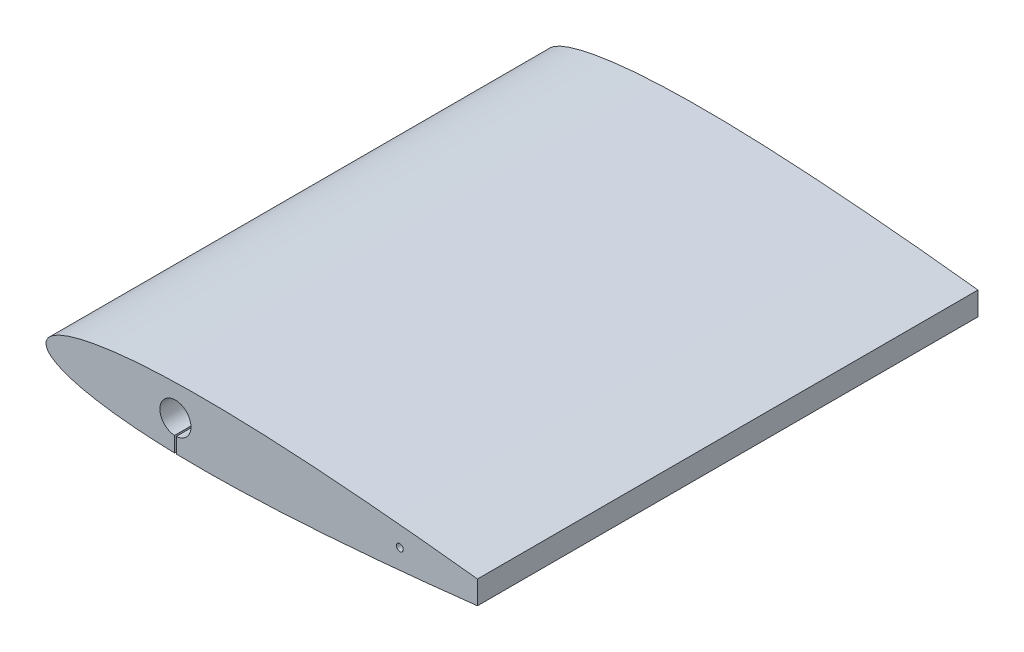
SolidWorks part; units mm, degrees
material "UoS Blue Foam"
ref_plane "Front Plane" through (0, 0, 0) normal (0, 0, 1) x (1, 0, 0)
ref_plane "Top Plane" through (0, 0, 0) normal (0, 1, 0) x (1, 0, 0)
ref_plane "Right Plane" through (0, 0, 0) normal (1, 0, 0) x (0, 0, -1)
sketch "Sketch5" plane through (0, 0, 0) normal (0, 0, 1) x (1, 0, 0)
  line L1 (300, 0.378) -> (300, -0.378)
  spline S1 degree 3 poles (300, 0.378) (299.2704, 0.4794) (297.2347, 0.7625) (293.6597, 1.2577) (289.1124, 1.8742) (284.0808, 2.5445) (278.752, 3.2381) (273.2659, 3.9349) (267.706, 4.629) (262.1146, 5.3131) (256.5083, 5.9822) (250.8917, 6.638) (245.2696, 7.2818) (239.6473, 7.9122) (234.0251, 8.527) (228.3991, 9.1262) (222.7683, 9.7131) (217.1359, 10.2875) (211.5054, 10.8469) (205.8776, 11.3916) (200.2515, 11.9209) (194.6264, 12.4346) (189.0028, 12.9319) (183.3815, 13.4131) (177.7632, 13.8764) (172.1483, 14.3212) (166.5375, 14.7478) (160.9317, 15.1542) (155.3317, 15.5391) (149.7375, 15.9026) (144.1487, 16.2418) (138.5657, 16.5574) (132.9909, 16.8474) (127.4274, 17.1102) (121.8776, 17.3439) (116.3408, 17.5453) (110.8155, 17.7127) (105.3013, 17.8445) (99.8006, 17.9401) (94.3174, 17.9966) (88.8558, 18.0101) (83.4186, 17.9792) (78.0085, 17.8992) (72.6285, 17.767) (67.2827, 17.5794) (61.9774, 17.3315) (56.7207, 17.021) (51.5252, 16.641) (46.4082, 16.1902) (41.3942, 15.6617) (36.5157, 15.054) (31.819, 14.3656) (27.3662, 13.6035) (23.2352, 12.7826) (19.5026, 11.9203) (16.2183, 11.0446) (13.3892, 10.1751) (10.9849, 9.3335) (8.9616, 8.5221) (7.2673, 7.747) (5.8461, 7.0106) (4.6477, 6.3006) (3.6282, 5.6065) (2.7519, 4.9266) (2.0063, 4.2499) (1.3906, 3.5703) (0.901, 2.8909) (0.5293, 2.2202) (0.2605, 1.5665) (0.0857, 0.931) (-0.0035, 0.309) (-0.0035, -0.309) (0.0857, -0.931) (0.2605, -1.5665) (0.5293, -2.2202) (0.901, -2.8909) (1.3906, -3.5703) (2.0063, -4.2499) (2.7519, -4.9266) (3.6282, -5.6065) (4.6477, -6.3006) (5.8461, -7.0106) (7.2673, -7.747) (8.9616, -8.5221) (10.9849, -9.3335) (13.3892, -10.1751) (16.2183, -11.0446) (19.5026, -11.9203) (23.2352, -12.7826) (27.3661, -13.6036) (31.8191, -14.3651) (36.5156, -15.0541) (41.3942, -15.6616) (46.4082, -16.1902) (51.5252, -16.641) (56.7207, -17.021) (61.9774, -17.3315) (67.2827, -17.5794) (72.6285, -17.767) (78.0085, -17.8992) (83.4186, -17.9792) (88.8558, -18.0101) (94.3174, -17.9966) (99.8006, -17.9401) (105.3013, -17.8445) (110.8155, -17.7127) (116.3408, -17.5453) (121.8776, -17.3439) (127.4274, -17.1102) (132.9909, -16.8474) (138.5657, -16.5574) (144.1487, -16.2418) (149.7375, -15.9026) (155.3317, -15.5391) (160.9317, -15.1542) (166.5375, -14.7478) (172.1483, -14.3212) (177.7632, -13.8764) (183.3815, -13.4131) (189.0028, -12.9319) (194.6264, -12.4346) (200.2515, -11.9209) (205.8776, -11.3916) (211.5054, -10.8469) (217.1359, -10.2875) (222.7683, -9.7131) (228.3991, -9.1262) (234.0251, -8.527) (239.6473, -7.9122) (245.2696, -7.2818) (250.8917, -6.638) (256.5083, -5.9822) (262.1146, -5.3131) (267.706, -4.629) (273.2659, -3.9349) (278.752, -3.2381) (284.0808, -2.5445) (289.1124, -1.8742) (293.6597, -1.2577) (297.2347, -0.7625) (299.2704, -0.4794) (300, -0.378) knots 0 0 0 0 0.003612 0.010079 0.017699 0.026115 0.034971 0.04405 0.053234 0.062448 0.071674 0.080921 0.090178 0.099424 0.108664 0.117912 0.12717 0.136427 0.145675 0.154916 0.164153 0.173387 0.182616 0.191838 0.201053 0.21026 0.219459 0.228647 0.237822 0.246985 0.256137 0.265279 0.274407 0.283512 0.292592 0.301646 0.310682 0.319699 0.328695 0.33766 0.346589 0.355477 0.364323 0.373122 0.381868 0.390553 0.399166 0.40769 0.416098 0.424355 0.432412 0.440205 0.447631 0.454564 0.460855 0.466413 0.471229 0.475366 0.478901 0.481915 0.484499 0.486747 0.488741 0.490543 0.492182 0.493673 0.495032 0.496279 0.497425 0.49849 0.499503 0.500497 0.50151 0.502575 0.503721 0.504968 0.506327 0.507818 0.509457 0.511259 0.513253 0.515501 0.518085 0.521099 0.524634 0.528771 0.533587 0.539145 0.545436 0.55237 0.559795 0.567588 0.575645 0.583902 0.59231 0.600834 0.609447 0.618132 0.626878 0.635677 0.644523 0.653411 0.66234 0.671305 0.680301 0.689318 0.698354 0.707408 0.716488 0.725593 0.734721 0.743863 0.753015 0.762178 0.771353 0.780541 0.78974 0.798947 0.808162 0.817384 0.826613 0.835847 0.845084 0.854325 0.863573 0.87283 0.882088 0.891336 0.900576 0.909822 0.919079 0.928326 0.937552 0.946766 0.95595 0.965029 0.973885 0.982301 0.989921 0.996388 1 1 1 1
  dimension "Tail chord" = 300
extrude "Boss-Extrude1" add sketch "Sketch5" along normal blind 290
ref_plane "Plane1" through (0, 0, 290) normal (0, 0, 1) x (1, 0, 0)
sketch "Sketch7" plane through (0, 0, 290) normal (0, 0, 1) x (1, 0, 0)
  line L0 (-6.7213, 0) -> (341.1075, 0) construction
  line L1 (300, -35.2391) -> (300, 43.1318) construction
  line L2 (300, -0.378) -> (300, 0.378) construction
  line L3 (0, 36.9496) -> (0, -37.0407) construction
  circle A0 centre (75, 0) radius 9
  dimension "D1" = 18
  dimension "Tail chord quarter" = 75
extrude "Cut-Extrude7" cut sketch "Sketch7" against normal through all
curve "Curve6"
  spline degree 3 poles (298.242, -0.1932, 0) (300.4407, 0, 0) (298.242, 0.1932, 0) (296.4349, 0.5367, 0) (292.0253, 1.0976, 0) (286.5771, 1.8592, 0) (279.4156, 2.8001, 0) (270.9173, 3.8949, 0) (261.066, 5.1159, 0) (250.0071, 6.4339, 0) (237.8495, 7.8187, 0) (224.7304, 9.2395, 0) (210.7923, 10.6647, 0) (196.1883, 12.0613, 0) (181.0783, 13.3946, 0) (165.6277, 14.6278, 0) (150.0058, 15.7225, 0) (134.3834, 16.6392, 0) (118.9317, 17.3387, 0) (103.8195, 17.7845, 0) (89.2123, 17.9443, 0) (75.2698, 17.7935, 0) (62.1444, 17.3161, 0) (49.9793, 16.5075, 0) (38.907, 15.374, 0) (29.0471, 13.9333, 0) (20.5034, 12.2128, 0) (13.3641, 10.246, 0) (7.6828, 8.0707, 0) (3.4992, 5.7028, 0) (0.7348, 3.1014, 0) (-0.3264, 0, 0) (0.7348, -3.1014, 0) (3.4992, -5.7028, 0) (7.6828, -8.0707, 0) (13.3641, -10.246, 0) (20.5034, -12.2128, 0) (29.0471, -13.9333, 0) (38.907, -15.374, 0) (49.9793, -16.5075, 0) (62.1444, -17.3161, 0) (75.2698, -17.7935, 0) (89.2123, -17.9443, 0) (103.8195, -17.7845, 0) (118.9317, -17.3387, 0) (134.3834, -16.6392, 0) (150.0058, -15.7225, 0) (165.6277, -14.6278, 0) (181.0783, -13.3946, 0) (196.1883, -12.0613, 0) (210.7923, -10.6647, 0) (224.7304, -9.2395, 0) (237.8495, -7.8187, 0) (250.0071, -6.4339, 0) (261.066, -5.1159, 0) (270.9173, -3.8949, 0) (279.4156, -2.8001, 0) (286.5771, -1.8592, 0) (292.0253, -1.0976, 0) (296.4349, -0.5367, 0) (298.242, -0.1932, 0) (300.4407, 0, 0) (298.242, 0.1932, 0) knots -0.012119 -0.005412 -0.001357 0 0.001357 0.005412 0.012119 0.021403 0.033159 0.047255 0.063534 0.081814 0.101892 0.123547 0.146538 0.170613 0.195504 0.220938 0.246636 0.272314 0.297694 0.3225 0.346466 0.36934 0.390884 0.410879 0.429129 0.445462 0.459736 0.471848 0.481751 0.489494 0.495334 0.5 0.504666 0.510506 0.518249 0.528152 0.540264 0.554538 0.570871 0.589121 0.609116 0.63066 0.653534 0.6775 0.702306 0.727686 0.753364 0.779062 0.804496 0.829387 0.853462 0.876453 0.898108 0.918186 0.936466 0.952745 0.966841 0.978597 0.987881 0.994588 0.998643 1 1.001357 1.005412 1.012119 periodic
sketch "Sketch8" plane through (0, 0, 0) normal (0, 1, 0) x (1, 0, 0)
  line L0 (300, 0) -> (0, 0) construction
  line L1 (152.9201, -127.685) -> (197.0801, -127.685)
  line L2 (152.9201, -127.685) -> (152.9201, -162.315)
  line L3 (152.9201, -162.315) -> (197.0801, -162.315)
  line L4 (197.0801, -127.685) -> (197.0801, -162.315)
  dimension "Servo slot width" = 34.63
  dimension "Servo slot length" = 44.16
  dimension "D3" = 127.685
  dimension "Slot post" = 152.92
extrude "Cut-Extrude8" cut sketch "Sketch8" against normal blind 50
sketch "Sketch10" plane through (0, 0, 0) normal (0, 1, 0) x (1, 0, 0)
  line L0 (300, 0) -> (0.0001, 0) construction
  line L1 (300, -290) -> (250, -290)
  line L2 (300, -290) -> (300, 0)
  line L3 (300, 0) -> (250, 0)
  line L4 (250, -290) -> (250, 0)
  dimension "Elevator" = 50
extrude "Cut-Extrude9" cut sketch "Sketch10" against normal blind 50 and the other way blind 50
sketch "Sketch12" plane through (0, 0, 0) normal (0, 1, 0) x (1, 0, 0)
  line L0 (300, 0) -> (0, 0) construction
  line L1 (74.5001, 0) -> (75.5001, 0)
  line L2 (74.5001, 0) -> (74.5001, -290)
  line L3 (74.5001, -290) -> (75.5001, -290)
  line L4 (75.5001, 0) -> (75.5001, -290)
  line L5 (66, -290) -> (84, -290) construction
  line L6 (0.0001, 0) -> (0.0001, -290) construction
  dimension "D1" = 1
  dimension "D2" = 74.5
extrude "Cut-Extrude10" cut sketch "Sketch12" against normal blind 50
sketch "Sketch13" plane through (0, 0, 0) normal (0, 0, 1) x (1, 0, 0)
  circle A0 centre (205, 0) radius 2
  dimension "D1" = 4
  dimension "Small hole" = 205
extrude "Cut-Extrude11" cut sketch "Sketch13" along normal blind 20
sketch "Sketch14" plane through (0, 0, 290) normal (0, 0, 1) x (1, 0, 0)
  circle A0 centre (205, 0) radius 2
  dimension "D1" = 4
  dimension "anti rotation peg" = 205
extrude "Cut-Extrude12" cut sketch "Sketch14" against normal blind 20
equation "\"Tail chord quarter@Sketch7\" = \"Tail chord@Sketch5\" * 0.25"
equation "\"D3@Sketch8\" = \"Horizontal stabiliser width@Boss-Extrude1\" / 2 - \"Servo slot width@Sketch8\" / 2"
equation "\"Elevator length\"= 50mm'Elevator cut"
equation "\"Elevator@Sketch10\"= \"Elevator length\""
equation "\"D2@Sketch12\"=\"Tail chord quarter@Sketch7\"-0.5"
equation "\"Small hole@Sketch13\"=\"Tail chord quarter@Sketch7\"*3-20"
equation "\"anti rotation peg@Sketch14\"=\"Small hole@Sketch13\""
equation "\"Slot post@Sketch8\" =  ( \"Tail chord@Sketch5\" - \"Elevator@Sketch10\" )  / 2 - \"Servo slot length@Sketch8\" / 2 + 50"
equation "\"Chord\"= 300mm'Tail chord"
equation "\"Tail chord@Sketch5\"=\"Chord\""
